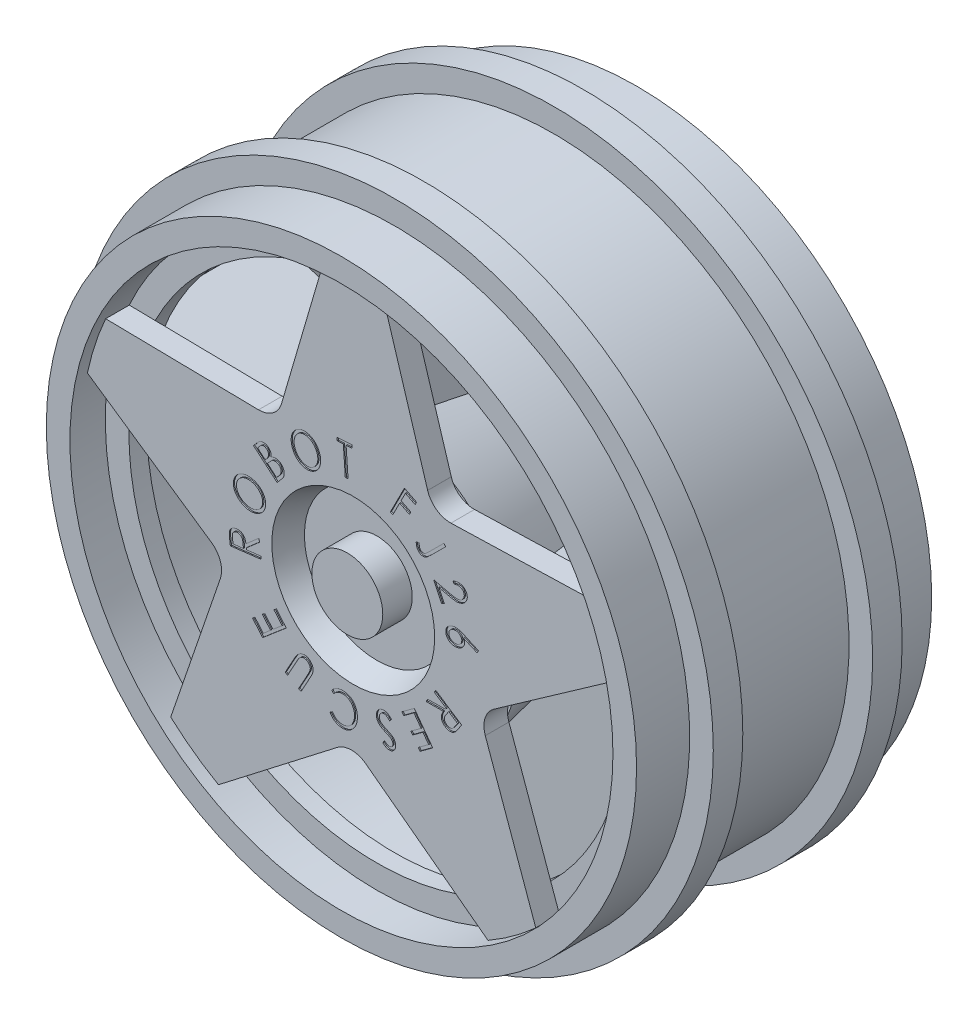
SolidWorks part; units mm, degrees
ref_plane "Alzado" through (0, 0, 0) normal (0, 0, 1) x (1, 0, 0)
ref_plane "Planta" through (0, 0, 0) normal (0, 1, 0) x (1, 0, 0)
ref_plane "Vista lateral" through (0, 0, 0) normal (1, 0, 0) x (0, 0, -1)
sketch "Croquis1" plane through (0, 0, 0) normal (0, 0, 1) x (1, 0, 0)
  circle A0 centre (0, 0) radius 25
  dimension "D1" = 50
extrude "Saliente-Extruir1" add sketch "Croquis1" along normal blind 25
sketch "Croquis2" plane through (0, 0, 25) normal (0, 0, 1) x (1, 0, 0)
  circle A0 centre (0, 0) radius 23
  circle A1 centre (0, 0) radius 25 construction
  dimension "D1" = 2
extrude "Cortar-Extruir1" cut sketch "Croquis2" against normal blind 1
sketch "Croquis3" plane through (0, 0, 24) normal (0, 0, 1) x (1, 0, 0)
  line L0 (0, 22.8637) -> (0, 23) construction
  line L2 (-2.5, 22.8637) -> (-6.5, 9.8012) construction
  line L9 (11.9191, -2.7554) -> (11.9213, -2.7532)
  line L10 (-11.2629, -4.7798) -> (-11.2623, -4.7767)
  line L11 (1.0626, -12.1872) -> (1.0654, -12.1886)
  line L12 (6.3024, 10.4871) -> (6.3038, 10.4842)
  line L19 (-7.3129, 9.2106) -> (-20.9722, 9.4429) construction
  line L21 (-2.5, 22.8637) -> (-6.0717, 10.6725)
  line L22 (-8.0231, 9.235) -> (-20.9722, 9.4429)
  line L23 (2.5, 22.8637) -> (6.3024, 10.4871)
  line L25 (22.5172, 4.6876) -> (11.9213, -2.7532)
  line L26 (20.9722, 9.4429) -> (8.2739, 9.0725)
  line L27 (11.4164, -19.9666) -> (1.0654, -12.1886)
  line L28 (15.4615, -17.0277) -> (11.1852, -5.0654)
  line L29 (-15.4615, -17.0277) -> (-11.2629, -4.7798)
  line L30 (-11.4164, -19.9666) -> (-1.361, -12.2031)
  line L31 (-20.9722, 9.4429) -> (-8.0263, 9.2346)
  line L32 (-22.5172, 4.6876) -> (-12.0264, -2.4766)
  circle A0 centre (0, 0) radius 23 construction
  circle A1 centre (0, 0) radius 23 construction
  arc A3 (-6.0717, 10.6725) -> (-8.0231, 9.235) centre (-7.991, 11.2348) cw
  arc A6 (8.2739, 9.0725) -> (6.3038, 10.4842) centre (8.2156, 11.0717) cw
  arc A8 (11.1852, -5.0654) -> (11.9191, -2.7554) centre (13.0685, -4.3921) cw
  arc A10 (-1.361, -12.2031) -> (1.0626, -12.1872) centre (-0.1388, -13.7861) cw
  arc A11 (-8.0263, 9.2346) -> (-6.2433, 10.6704) centre (-8.1634, 11.2299) ccw
  arc A12 (-12.0264, -2.4766) -> (-11.2623, -4.7767) centre (-13.1543, -4.1282) cw
  arc A14 (-2.5, 22.8637) -> (-20.9722, 9.4429) centre (0, 0) ccw
  arc A15 (-22.5172, 4.6876) -> (-15.4615, -17.0277) centre (0, 0) ccw
  arc A16 (-11.4164, -19.9666) -> (11.4164, -19.9666) centre (0, 0) ccw
  arc A18 (15.4615, -17.0277) -> (22.5172, 4.6876) centre (0, 0) ccw
  arc A19 (20.9722, 9.4429) -> (0, 23) centre (0, 0) ccw
  point P31 (0, 0)
  point P71 (0, 0)
  dimension "D5" = 2
  dimension "D1" = 2.5
  dimension "D7" = 5
extrude "Cortar-Extruir2" cut sketch "Croquis3" against normal blind 25
sketch "Croquis4" plane through (0, 0, 24) normal (0, 0, 1) x (1, 0, 0)
  circle A0 centre (0, 0) radius 7.5
  dimension "D1" = 15
extrude "Cortar-Extruir3" cut sketch "Croquis4" against normal blind 2.5
sketch "Croquis6" plane through (0, 0, 0) normal (1, 0, 0) x (0, 0, -1)
  line L0 (-20.3379, 0) -> (-20.3379, 23.995) construction
  line L1 (-20.3379, 0) -> (0, 0) construction
  line L2 (-20.3379, 5.5) -> (-28.5383, 5.5) construction
  line L3 (-20.3379, 7.5) -> (-24, 7.5)
  line L4 (-25, 25) -> (-25, -25) construction
  line L5 (-24, 7.5) -> (-24, 6.9)
  line L6 (-24, 6.9) -> (-20.3379, 5.5)
  line L7 (-20.3379, 7.5) -> (-20.3379, 5.5)
  dimension "D1" = 2
  dimension "D2" = 1
  dimension "D3" = 0.6
  dimension "D4" = 5.5
revolve "Revolución1" add sketch "Croquis6" angle 360 about L1
sketch "Croquis7" plane through (0, 0, 21.5) normal (0, 0, 1) x (1, 0, 0)
  circle A0 centre (0, 0) radius 3
  dimension "D1" = 6
extrude "Saliente-Extruir2" add sketch "Croquis7" along normal blind 3
ref_plane "Plano1" through (0, 0, 22) normal (0, 0, 1) x (1, 0, 0)
sketch "Croquis11" plane through (0, 0, 22) normal (0, 0, 1) x (1, 0, 0)
  circle A0 centre (0, 0) radius 23
  circle A1 centre (0, 0) radius 20
  circle A2 centre (0, 0) radius 23 construction
  dimension "D1" = 3
extrude "Saliente-Extruir5" add sketch "Croquis11" against normal blind 1.5
sketch "Croquis14" plane through (0, 0, 0) normal (0, 0, -1) x (-1, 0, 0)
  circle A0 centre (0, 0) radius 23
extrude "Cortar-Extruir5" cut sketch "Croquis14" against normal up to vertex
sketch "Croquis15" plane through (0, 0, 20.5) normal (0, 0, -1) x (-1, 0, 0)
  circle A0 centre (0, 0) radius 21
extrude "Cortar-Extruir7" cut sketch "Croquis15" against normal up to vertex
sketch "Croquis16" plane through (0, 0, 0) normal (1, 0, 0) x (0, 0, -1)
  line L0 (6.6064, 0) -> (-38.7801, 0) construction
  line L1 (6.6064, 0) -> (6.6064, 7)
  line L2 (6.6064, 7) -> (2.6064, 7)
  line L3 (2.6064, 7) -> (-22, 12)
  line L4 (-22, 12) -> (-22, 0)
  line L5 (-22, 0) -> (6.6064, 0)
  line L6 (-25, 25) -> (-25, -25) construction
  dimension "D1" = 3
  dimension "D2" = 4
  dimension "D3" = 12
  dimension "D4" = 7
revolve "Revolución2" add sketch "Croquis16" angle 360 about L0
ref_plane "Plano2" through (0, 0, 9.1936) normal (0, 0, -1) x (-1, 0, 0)
sketch "Croquis17" plane through (0, 0, 9.1936) normal (0, 0, -1) x (-1, 0, 0)
  line L12 (-1.105, 1.3019) -> (-0.8802, 22.9832)
  line L14 (0.8967, 1.4532) -> (1.1198, 22.9727)
  line L15 (1.6592, -0.4038) -> (22.1944, 6.034)
  line L16 (0.8967, 1.4532) -> (21.5863, 7.9393)
  line L17 (0.1287, -1.7027) -> (12.5971, -19.2435)
  line L18 (1.6592, -0.4038) -> (14.2212, -18.0764)
  line L19 (-1.5796, -0.6486) -> (-14.409, -17.9271)
  line L20 (0.1287, -1.7027) -> (-12.7971, -19.1111)
  line L21 (-1.105, 1.3019) -> (-21.5023, 8.164)
  line L22 (-1.5796, -0.6486) -> (-22.1303, 6.2651)
  circle A11 centre (0, 0) radius 23 construction
  circle A20 centre (0, 0) radius 23 construction
  arc A25 (-21.5023, 8.164) -> (-22.1303, 6.2651) centre (0, 0) ccw
  arc A26 (1.1198, 22.9727) -> (-0.8802, 22.9832) centre (0, 0) ccw
  arc A27 (22.1944, 6.034) -> (21.5863, 7.9393) centre (0, 0) ccw
  arc A28 (12.5971, -19.2435) -> (14.2212, -18.0764) centre (0, 0) ccw
  arc A29 (-14.409, -17.9271) -> (-12.7971, -19.1111) centre (0, 0) ccw
  point P30 (1.0274, 0.7465)
  point P47 (0, 0)
  dimension "D1" = 2
  dimension "D2" = 5
extrude "Saliente-Extruir7" add sketch "Croquis17" against normal up to surface (12.8064 mm away) up to face at (-6.1354, 0, 22)
sketch "Croquis18" plane through (0, 0, -6.6064) normal (0, 0, -1) x (-1, 0, 0)
  circle A0 centre (0, 0) radius 3.15
  dimension "D1" = 6.3
extrude "Cortar-Extruir8" cut sketch "Croquis18" against normal blind 20 contours A0
sketch "Croquis27" plane through (0, 0, 24) normal (0, 0, 1) x (1, 0, 0)
  circle A0 centre (0, 0) radius 8 construction
  text T0 "RESCUE ROBOT FJ26" font "Century Gothic" height in points 10
  dimension "D1" = 16
extrude "Cortar-Extruir11" cut sketch "Croquis27" against normal blind 0.1
sketch "Croquis30" plane through (0, 0, 0) normal (1, 0, 0) x (0, 0, -1)
  line L0 (-12.5, 25) -> (-12.5, 29.7165) construction
  line L1 (0, 25) -> (-25, 25) construction
  line L2 (-20.5, 25) -> (-20.5, 27)
  line L3 (-20.5, 27) -> (-18, 27)
  line L4 (-18, 27) -> (-18, 25)
  line L5 (-18, 25) -> (-20.5, 25)
  line L6 (-25, 25) -> (-25, -25) construction
  line L7 (0, 0) -> (-13.1365, 0) construction
  line L8 (-7, 27) -> (-7, 25)
  line L9 (-4.5, 27) -> (-7, 27)
  line L10 (-4.5, 25) -> (-4.5, 27)
  line L11 (-7, 25) -> (-4.5, 25)
  dimension "D1" = 2
  dimension "D2" = 2.5
  dimension "D3" = 4.5
revolve "Revolución3" add sketch "Croquis30" angle 360 about L7
